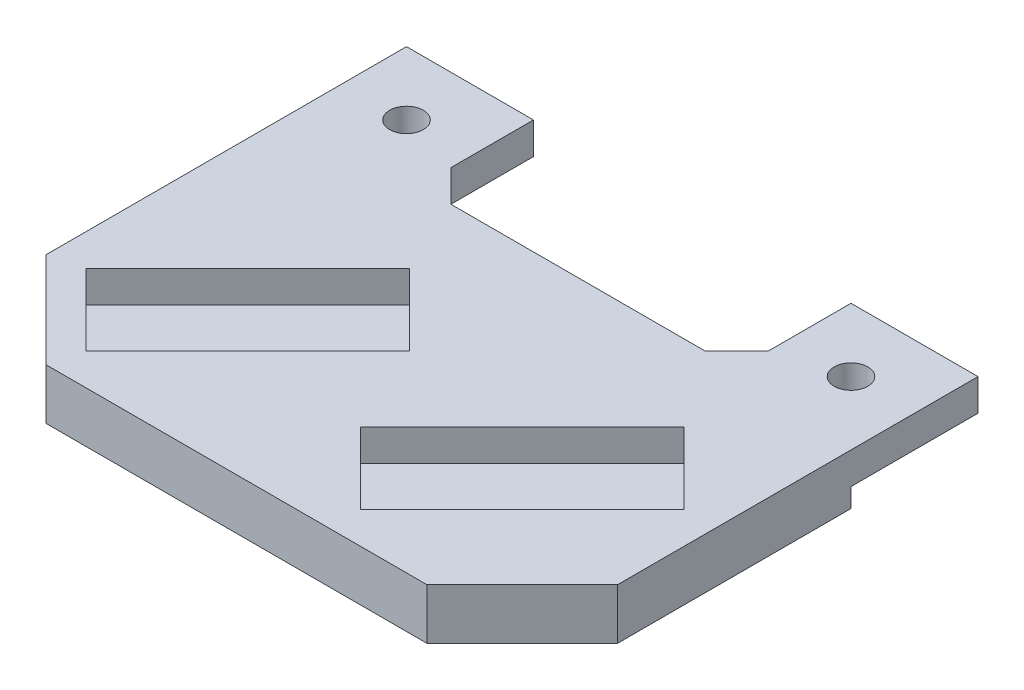
SolidWorks part; units mm, degrees
ref_plane "Front Plane" through (0, 0, 0) normal (0, 0, 1) x (1, 0, 0)
ref_plane "Top Plane" through (0, 0, 0) normal (0, 1, 0) x (1, 0, 0)
ref_plane "Right Plane" through (0, 0, 0) normal (1, 0, 0) x (0, 0, -1)
sketch "Sketch1" plane through (0, 0, 0) normal (0, 1, 0) x (1, 0, 0)
  line L0 (10, 10) -> (80, 10) construction
  line L1 (0, 0) -> (90, 0)
  line L2 (0, 0) -> (0, 20)
  line L3 (0, 20) -> (90, 20)
  line L4 (90, 0) -> (90, 20)
  line L5 (45, 20) -> (45, 0) construction
  line L6 (0, 10) -> (90, 10) construction
  line L7 (5, -35.4558) -> (16.3137, -46.7696)
  line L8 (0, 0) -> (90, 0)
  line L9 (0, 0) -> (0, -51.7696)
  line L10 (0, -51.7696) -> (90, -51.7696)
  line L11 (90, 0) -> (90, -51.7696)
  line L12 (16.3137, -46.7696) -> (41.7696, -21.3137)
  line L13 (41.7696, -21.3137) -> (30.4558, -10)
  line L14 (30.4558, -10) -> (5, -35.4558)
  line L15 (36.1127, -15.6569) -> (10.6569, -41.1127) construction
  line L16 (17.7279, -22.7279) -> (29.0416, -34.0416) construction
  line L17 (45, 0) -> (45, -51.7696) construction
  line L18 (48.2304, -35.4558) -> (59.5442, -46.7696)
  line L19 (59.5442, -46.7696) -> (85, -21.3137)
  line L20 (85, -21.3137) -> (73.6863, -10)
  line L21 (73.6863, -10) -> (48.2304, -35.4558)
  line L22 (79.3431, -15.6569) -> (53.8873, -41.1127) construction
  circle A0 centre (10, 10) radius 2.65
  circle A1 centre (80, 10) radius 2.65
  dimension "D2" = 5.3
  dimension "D1" = 90
  dimension "D3" = 20
  dimension "D4" = 36
  dimension "D5" = 16
  dimension "D6" = 45
  dimension "D7" = 5
  dimension "D8" = 5
  dimension "D9" = 10
  dimension "D10" = 36
  dimension "D11" = 16
  dimension "D12" = 5
  dimension "D13" = 5
  dimension "D14" = 10
  dimension "D15" = 10
  dimension "D16" = 10
extrude "Boss-Extrude1" add sketch "Sketch1" along normal blind 5 contours L11 L1 L9 L10 L21 L20 L19 L18 L14 L13 L12 L7 | L1 L4 L3 L2 A1 A0 region at (45, 0, -10) region at (45, 0, 25.0636)
sketch "Sketch2" plane through (0, 0, 0) normal (0, -1, 0) x (1, 0, 0)
  line L0 (90, -20) -> (90, 51.7696) construction
  line L1 (0, 51.7696) -> (90, 51.7696)
  line L2 (0, 51.7696) -> (0, 0)
  line L3 (0, 0) -> (90, 0)
  line L4 (90, 51.7696) -> (90, 0)
  dimension "D1" = 10
extrude "Boss-Extrude2" add sketch "Sketch2" along normal blind 3
sketch "Sketch3" plane through (0, 5, 0) normal (0, 1, 0) x (1, 0, 0)
  line L0 (0, 20) -> (90, 20) construction
  line L1 (20, 20) -> (70, 20)
  line L2 (20, 20) -> (20, 2)
  line L3 (20, 2) -> (70, 2)
  line L4 (70, 20) -> (70, 2)
  line L5 (45, 20) -> (45, 2) construction
  circle A0 centre (10, 10) radius 2.65 construction
  circle A1 centre (80, 10) radius 2.65 construction
  dimension "D2" = 10
  dimension "D1" = 12
extrude "Cut-Extrude1" cut sketch "Sketch3" against normal blind 5
chamfer "Chamfer1" distance 5 angle 45 2 edges at (20, 2.5, -2) (70, 2.5, -2)
chamfer "Chamfer2" distance 15 angle 45 2 edges at (90, 1, 51.7696) (0, 1, 51.7696)
